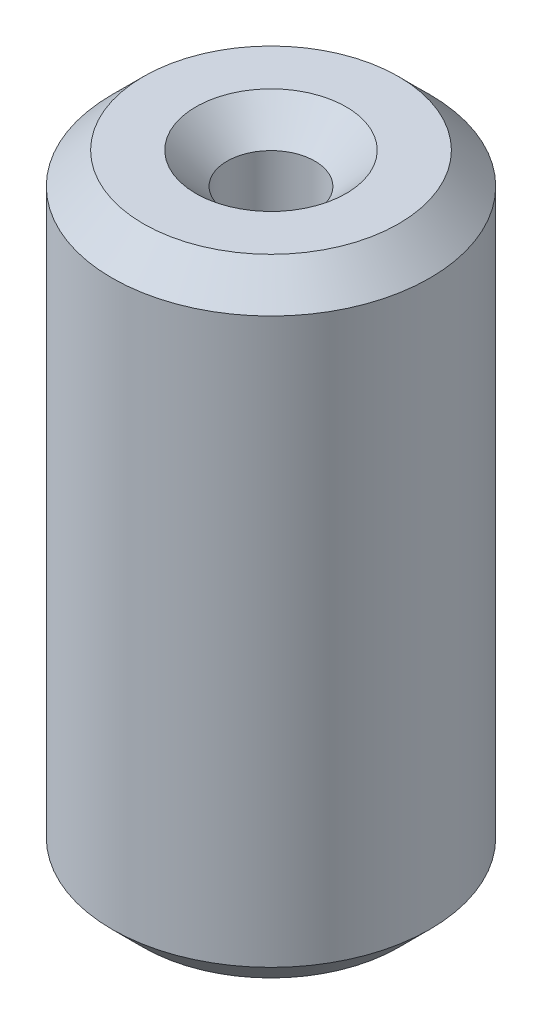
SolidWorks part; units mm, degrees
ref_plane "Front Plane" through (0, 0, 0) normal (0, 0, 1) x (1, 0, 0)
ref_plane "Top Plane" through (0, 0, 0) normal (0, 1, 0) x (1, 0, 0)
ref_plane "Right Plane" through (0, 0, 0) normal (1, 0, 0) x (0, 0, -1)
sketch "Sketch1" plane through (0, 0, 0) normal (0, 1, 0) x (1, 0, 0)
  circle A0 centre (0, 0) radius 5
  dimension "SLEEVE_OD" = 10
extrude "Boss-Extrude1" add sketch "Sketch1" along normal blind 19.7202
sketch "Sketch2" plane through (0, 0, 0) normal (0, 1, 0) x (1, 0, 0)
  circle A0 centre (0, 0) radius 1.3788
  dimension "BORE_D" = 2.7575
extrude "Cut-Extrude1" cut sketch "Sketch2" along normal through all
chamfer "Chamfer1" distance 0.9856 angle 45 4 edges at (0, 19.7202, 1.3788) (0, 0, 1.3788) (0, 0, 5) (0, 19.7202, 5)
